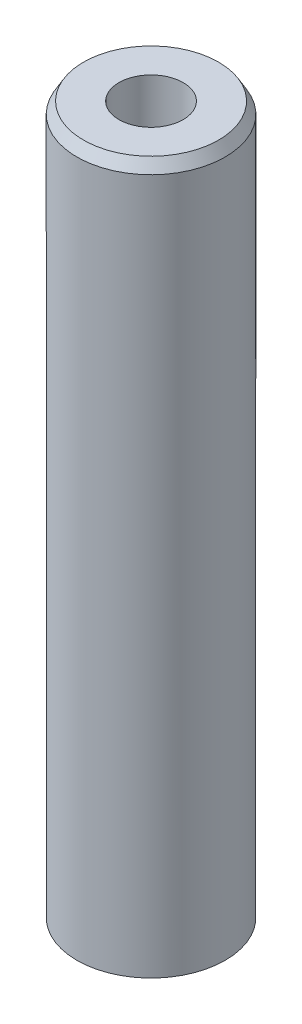
SolidWorks part; units mm, degrees
ref_plane "Front Plane" through (0, 0, 0) normal (0, 0, 1) x (1, 0, 0)
ref_plane "Top Plane" through (0, 0, 0) normal (0, 1, 0) x (1, 0, 0)
ref_plane "Right Plane" through (0, 0, 0) normal (1, 0, 0) x (0, 0, -1)
sketch "Sketch1" plane through (0, 0, 0) normal (0, 1, 0) x (1, 0, 0)
  circle A0 centre (0, 0) radius 5
  dimension "SHAFT_OD" = 10
extrude "Boss-Extrude1" add sketch "Sketch1" along normal blind 48.1346
sketch "Sketch2" plane through (0, 0, 0) normal (0, 1, 0) x (1, 0, 0)
  circle A0 centre (0, 0) radius 2.1662
  dimension "BORE_D" = 4.3324
extrude "Cut-Extrude1" cut sketch "Sketch2" along normal through all
chamfer "Chamfer1" distance 0.7677 angle 30 2 edges at (0, 48.1346, 5) (0, 0, 5) first distance on face at (0, 48.1346, 5) first distance on face at (0, 0, 2.1662)
